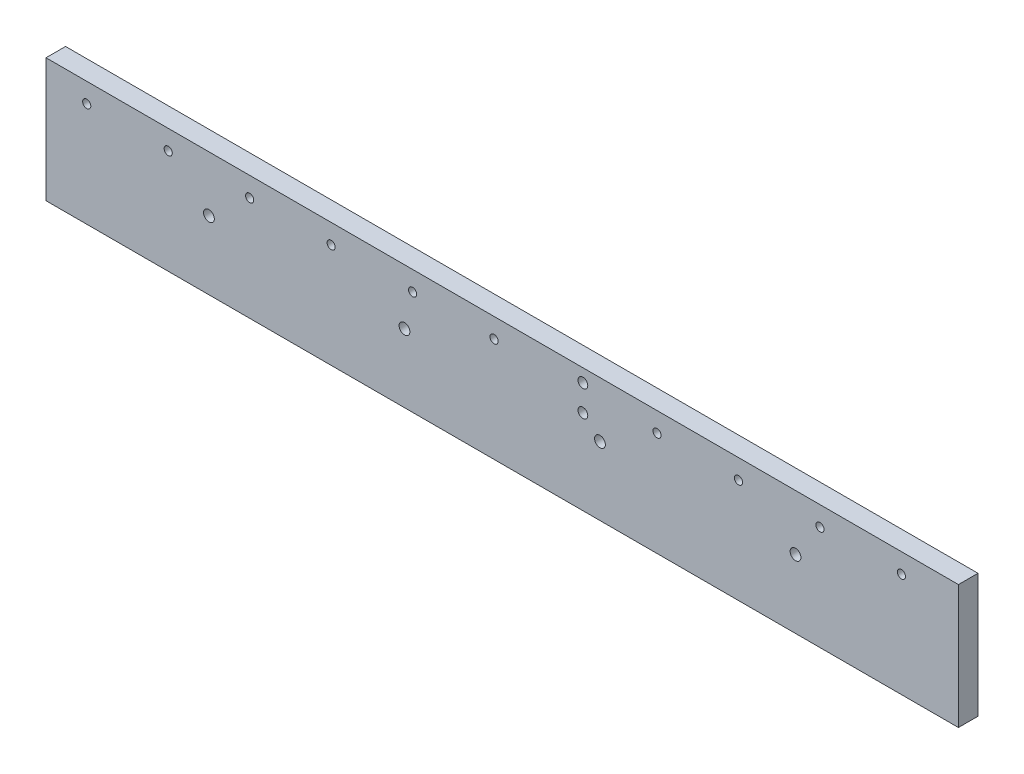
SolidWorks part; units mm, degrees
ref_plane "Front" through (0, 0, 0) normal (0, 0, 1) x (1, 0, 0)
ref_plane "Top" through (0, 0, 0) normal (0, 1, 0) x (1, 0, 0)
ref_plane "Right" through (0, 0, 0) normal (1, 0, 0) x (0, 0, -1)
sketch "Esquisse1" plane through (0, 0, 0) normal (0, 0, 1) x (1, 0, 0)
  line L1 (0, 0) -> (280, 0)
  line L2 (0, 0) -> (0, 38)
  line L3 (0, 38) -> (280, 38)
  line L4 (280, 0) -> (280, 38)
  dimension "D1" = 38
  dimension "D2" = 280
extrude "Boss.-Extru.1" add sketch "Esquisse1" along normal blind 6
sketch "Esquisse2" plane through (0, 0, 6) normal (0, 0, 1) x (1, 0, 0)
  line L0 (0, 32) -> (280, 32) construction
  line L1 (0, 38) -> (0, 0) construction
  line L2 (280, 0) -> (280, 38) construction
  line L3 (280, 38) -> (0, 38) construction
  line L4 (12.5, 32) -> (37.5, 32) construction
  circle A0 centre (12.5, 32) radius 1.25
  circle A1 centre (37.5, 32) radius 1.25
  circle A2 centre (62.5, 32) radius 1.25
  circle A3 centre (87.5, 32) radius 1.25
  circle A4 centre (112.5, 32) radius 1.25
  circle A5 centre (137.5, 32) radius 1.25
  circle A6 centre (162.5, 32) radius 1.25
  circle A7 centre (187.5, 32) radius 1.25
  circle A8 centre (212.5, 32) radius 1.25
  circle A9 centre (237.5, 32) radius 1.25
  circle A10 centre (262.5, 32) radius 1.25
  dimension "D1" = 12.5
  dimension "D2" = 2.5
  dimension "D3" = 6
  dimension "D5" = 25
  dimension "D4" = 11
extrude "Enlèv. mat.-Extru.1" cut sketch "Esquisse2" against normal up to vertex (6 mm away) up to point (280, 38, 0)
sketch "Esquisse5" plane through (0, 0, 6) normal (0, 0, 1) x (1, 0, 0)
  circle A0 centre (162.5, 32) radius 1.25
  circle A1 centre (162.5, 32) radius 1.25 construction
extrude "Boss.-Extru.2" add sketch "Esquisse5" against normal up to vertex (6 mm away) up to point (280, 38, 0)
sketch "Esquisse3" plane through (0, 0, 6) normal (0, 0, 1) x (1, 0, 0)
  line L0 (0, 21) -> (280, 21) construction
  line L1 (0, 38) -> (0, 0) construction
  line L2 (280, 0) -> (280, 38) construction
  line L3 (50, 21) -> (110, 21) construction
  line L4 (170, 21) -> (170, 0.0547) construction
  line L5 (0, 0) -> (280, 0) construction
  line L6 (110, 21) -> (110, 0.0547) construction
  line L7 (110, 0.0547) -> (170, 0.0547) construction
  line L8 (140, 0.0547) -> (140, 21) construction
  circle A0 centre (50, 21) radius 1.65
  circle A1 centre (110, 21) radius 1.65
  circle A2 centre (170, 21) radius 1.65
  circle A3 centre (230, 21) radius 1.65
  dimension "D1" = 3.3
  dimension "D3" = 60
  dimension "D4" = 21
  dimension "D2" = 4
extrude "Enlèv. mat.-Extru.2" cut sketch "Esquisse3" against normal through all and the other way through all
sketch "Esquisse4" plane through (0, 0, 6) normal (0, 0, 1) x (1, 0, 0)
  line L0 (164.75, 26) -> (164.75, 34) construction
  line L1 (164.75, 34) -> (164.75, 38) construction
  line L2 (280, 38) -> (0, 38) construction
  line L3 (0, 38) -> (0, 0) construction
  line L4 (0, 0) -> (280, 0) construction
  circle A0 centre (164.75, 34) radius 1.5
  circle A1 centre (164.75, 26) radius 1.5
  dimension "D1" = 8
  dimension "D2" = 34
  dimension "D3" = 3
  dimension "D4" = 164.75
extrude "Enlèv. mat.-Extru.3" cut sketch "Esquisse4" against normal through all and the other way through all
